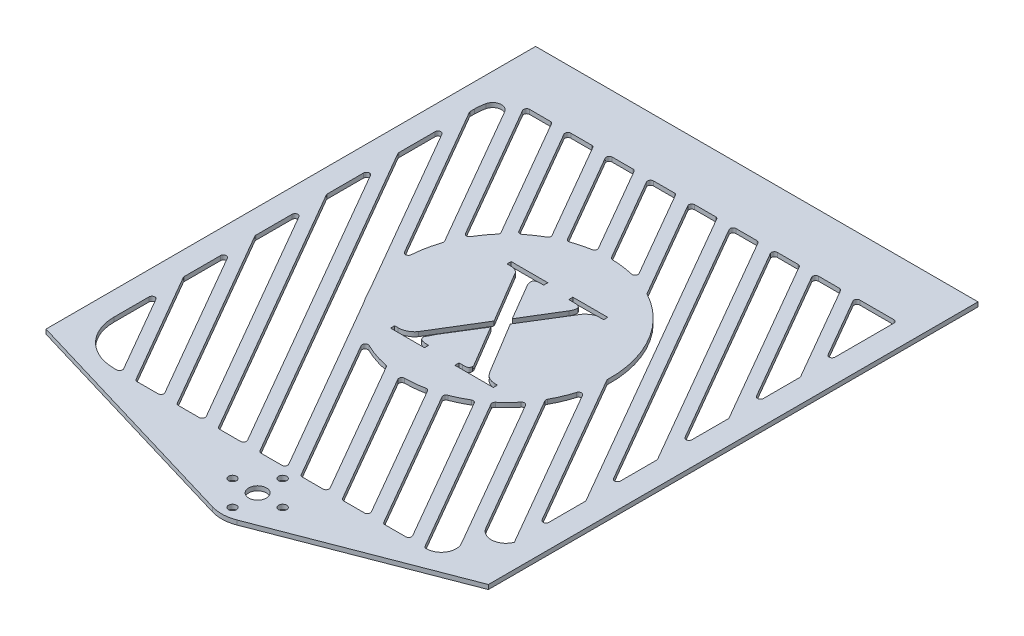
SolidWorks part; units mm, degrees
ref_plane "前视基准面" through (0, 0, 0) normal (0, 0, 1) x (1, 0, 0)
ref_plane "上视基准面" through (0, 0, 0) normal (0, 1, 0) x (1, 0, 0)
ref_plane "右视基准面" through (0, 0, 0) normal (1, 0, 0) x (0, 0, -1)
sketch "草图1" plane through (0, 0, 0) normal (0, 1, 0) x (1, 0, 0)
  circle A0 centre (0, 0) radius 12.25
  circle A1 centre (0, 0) radius 8.5 construction
  circle A2 centre (0, 8.5) radius 1.35
  circle A3 centre (8.5, 0) radius 1.35
  circle A4 centre (0, -8.5) radius 1.35
  circle A5 centre (-8.5, 0) radius 1.35
  circle A6 centre (0, 0) radius 3
  point P15 (0, 0)
  dimension "D1" = 24.5
  dimension "D2" = 17
  dimension "D3" = 2.7
  dimension "D5" = 6
  dimension "D4" = 4
extrude "凸台-拉伸1" add sketch "草图1" along normal blind 1.5
sketch "草图2" plane through (0, 1.5, 0) normal (0, 1, 0) x (1, 0, 0)
  line L0 (-84, 12.25) -> (-3.4985, -11.7398)
  line L1 (-84, 167.25) -> (66, 167.25)
  line L2 (-84, 167.25) -> (-84, 12.25)
  line L4 (66, 167.25) -> (66, 12.25)
  line L5 (4.3959, -11.4341) -> (66, 12.25)
  circle A0 centre (0, 0) radius 12.25 construction
  arc A2 (4.3959, -11.4341) -> (-3.4985, -11.7398) centre (0, 0) ccw
  dimension "D7" = 24.5
  dimension "D1" = 155
  dimension "D2" = 150
  dimension "D3" = 66
  dimension "D5" = 155
  dimension "D6" = 106.594
extrude "凸台-拉伸2" add sketch "草图2" against normal up to surface (1.5 mm away) up to face at (0, 0, 12.25)
sketch "草图4" plane through (0, 1.5, 0) normal (0, 1, 0) x (1, 0, 0)
  line L5 (-84, 167.25) -> (-84, 12.25) construction
  circle A0 centre (0, 0) radius 12.25 construction
  text T0 "X" font "新宋体" height 40
  dimension "D1" = 24.5
  dimension "D2" = 70
  dimension "D3" = 56
extrude "切除-拉伸2" cut sketch "草图4" against normal through all
sketch "草图5" plane through (0, 1.5, 0) normal (0, 1, 0) x (1, 0, 0)
  line L0 (66, 12.25) -> (66, 167.25) construction
  line L1 (66, 167.25) -> (-84, 167.25) construction
  line L2 (66, 12.25) -> (-84, 12.25)
  line L3 (66, 12.25) -> (66, 166.75)
  line L4 (66, 166.75) -> (-84, 166.75)
  line L5 (-84, 12.25) -> (-84, 166.75)
  line L7 (58, 12.25) -> (58, 158.75)
  line L8 (58, 158.75) -> (-76, 158.75)
  line L9 (-76, 12.25) -> (-76, 158.75)
  line L10 (58, 20.25) -> (-76, 20.25) construction
  line L11 (58, 20.25) -> (58, 158.75) construction
  line L12 (-76, 20.25) -> (-76, 158.75) construction
  line L13 (-53.6906, 12.25) -> (-76, 50.891)
  line L14 (-56, 12.25) -> (-76, 46.891)
  line L15 (-42, 12.25) -> (-76, 71.1397)
  line L16 (-28, 12.25) -> (-76, 95.3884)
  line L17 (-14, 12.25) -> (-76, 119.6372)
  line L18 (0, 12.25) -> (-31.5075, 66.8226)
  line L19 (14, 12.25) -> (-12.901, 58.8439)
  line L20 (28, 12.25) -> (0.471, 59.9316)
  line L21 (42, 12.25) -> (11.4265, 65.2048)
  line L22 (56, 12.25) -> (20.1779, 74.2958)
  line L23 (58, 33.0346) -> (25.6921, 88.9935)
  line L24 (58, 57.2833) -> (-0.5818, 158.75)
  line L25 (58, 81.532) -> (13.4182, 158.75)
  line L26 (58, 105.7807) -> (27.4182, 158.75)
  line L27 (-43.9794, 92.4245) -> (-76, 147.8859)
  line L29 (-39.6906, 12.25) -> (-76, 75.1397)
  line L30 (-25.6906, 12.25) -> (-76, 99.3884)
  line L31 (-11.6906, 12.25) -> (-76, 123.6372)
  line L32 (2.3094, 12.25) -> (-27.5301, 63.9335)
  line L33 (16.3094, 12.25) -> (-10.4839, 58.6573)
  line L34 (30.3094, 12.25) -> (2.427, 60.5438)
  line L35 (44.3094, 12.25) -> (13.0295, 66.4284)
  line L36 (58, 12.7859) -> (21.3707, 76.2298)
  line L37 (58, 37.0346) -> (25.9816, 92.4921)
  line L38 (58, 61.2833) -> (1.7276, 158.75)
  line L39 (58, 85.532) -> (15.7276, 158.75)
  line L40 (58, 109.7807) -> (29.7276, 158.75)
  line L41 (-43.466, 87.5353) -> (-76, 143.8859)
  line L42 (-58.3094, 12.25) -> (-76, 42.891)
  line L43 (-44.3094, 12.25) -> (-76, 67.1397)
  line L44 (-30.3094, 12.25) -> (-76, 91.3884)
  line L45 (-16.3094, 12.25) -> (-76, 115.6372)
  line L46 (-2.3094, 12.25) -> (-37.8559, 73.8183)
  line L47 (11.6906, 12.25) -> (-15.4282, 59.2212)
  line L48 (25.6906, 12.25) -> (-1.5479, 59.4284)
  line L49 (39.6906, 12.25) -> (9.7655, 64.0817)
  line L50 (53.6906, 12.25) -> (18.9052, 72.5)
  line L51 (58, 29.0346) -> (25.1457, 85.94)
  line L52 (58, 53.2833) -> (-2.8912, 158.75)
  line L53 (58, 77.532) -> (11.1088, 158.75)
  line L54 (58, 101.7807) -> (25.1088, 158.75)
  line L55 (-40.5818, 78.5397) -> (-76, 139.8859)
  line L56 (-42.0094, 105.2611) -> (-72.8912, 158.75)
  line L57 (-41.0725, 107.6384) -> (-70.5818, 158.75)
  line L58 (-40.0256, 109.825) -> (-68.2724, 158.75)
  line L59 (-34.8898, 117.1783) -> (-58.8912, 158.75)
  line L60 (-33.4445, 118.6751) -> (-56.5818, 158.75)
  line L61 (113.7321, 13.25) -> (24.5314, 167.75) construction
  line L62 (112, 12.25) -> (22.7994, 166.75) construction
  line L63 (110.2679, 11.25) -> (21.0673, 165.75) construction
  line L64 (-31.9364, 120.0629) -> (-54.2724, 158.75)
  line L65 (99.7321, 13.25) -> (10.5314, 167.75) construction
  line L66 (98, 12.25) -> (8.7994, 166.75) construction
  line L67 (96.2679, 11.25) -> (7.0673, 165.75) construction
  line L68 (-25.2032, 124.6493) -> (-44.8912, 158.75)
  line L69 (85.7321, 13.25) -> (-3.4686, 167.75) construction
  line L70 (84, 12.25) -> (-5.2006, 166.75) construction
  line L71 (82.2679, 11.25) -> (-6.9327, 165.75) construction
  line L72 (-23.4001, 125.5263) -> (-42.5818, 158.75)
  line L73 (71.7321, 13.25) -> (-17.4686, 167.75) construction
  line L74 (70, 12.25) -> (-19.2006, 166.75) construction
  line L75 (-57.7321, 11.25) -> (-146.9327, 165.75) construction
  line L76 (-56, 12.25) -> (-145.2006, 166.75) construction
  line L77 (-54.2679, 13.25) -> (-143.4686, 167.75) construction
  line L78 (-43.7321, 11.25) -> (-132.9327, 165.75) construction
  line L79 (-42, 12.25) -> (-131.2006, 166.75) construction
  line L80 (-40.2679, 13.25) -> (-129.4686, 167.75) construction
  line L81 (-29.7321, 11.25) -> (-118.9327, 165.75) construction
  line L82 (-28, 12.25) -> (-117.2006, 166.75) construction
  line L83 (-26.2679, 13.25) -> (-115.4686, 167.75) construction
  line L84 (-15.7321, 11.25) -> (-104.9327, 165.75) construction
  line L85 (-14, 12.25) -> (-103.2006, 166.75) construction
  line L86 (-12.2679, 13.25) -> (-101.4686, 167.75) construction
  line L87 (-1.7321, 11.25) -> (-90.9327, 165.75) construction
  line L88 (0, 12.25) -> (-89.2006, 166.75) construction
  line L89 (1.7321, 13.25) -> (-87.4686, 167.75) construction
  line L90 (12.2679, 11.25) -> (-76.9327, 165.75) construction
  line L91 (14, 12.25) -> (-75.2006, 166.75) construction
  line L92 (-21.5389, 126.3027) -> (-40.2724, 158.75)
  line L93 (15.7321, 13.25) -> (-73.4686, 167.75) construction
  line L94 (26.2679, 11.25) -> (-62.9327, 165.75) construction
  line L95 (28, 12.25) -> (-61.2006, 166.75) construction
  line L96 (-13.3429, 128.3554) -> (-30.8912, 158.75)
  line L97 (29.7321, 13.25) -> (-59.4686, 167.75) construction
  line L98 (40.2679, 11.25) -> (-48.9327, 165.75) construction
  line L99 (42, 12.25) -> (-47.2006, 166.75) construction
  line L100 (-11.1514, 128.5596) -> (-28.5818, 158.75)
  line L101 (43.7321, 13.25) -> (-45.4686, 167.75) construction
  line L102 (54.2679, 11.25) -> (-34.9327, 165.75) construction
  line L103 (56, 12.25) -> (-33.2006, 166.75) construction
  line L104 (-8.8801, 128.6256) -> (-26.2724, 158.75)
  line L105 (57.7321, 13.25) -> (-31.4686, 167.75) construction
  line L106 (68.2679, 11.25) -> (-20.9327, 165.75) construction
  line L107 (58, 134.0295) -> (43.7276, 158.75)
  line L108 (58, 130.0295) -> (41.4182, 158.75)
  line L109 (58, 126.0295) -> (39.1088, 158.75)
  line L110 (1.4167, 127.0398) -> (-16.8912, 158.75)
  line L111 (4.3344, 125.9862) -> (-14.5818, 158.75)
  line L112 (7.5089, 124.4877) -> (-12.2724, 158.75)
  circle A0 centre (-9, 93.6258) radius 35
  point P2 (48.5544, 142.3897)
  dimension "D1" = 75
  dimension "D2" = 70
  dimension "D3" = 2
  dimension "D4" = 2
  dimension "D6" = 14.2724
  dimension "D7" = 24.7205
  dimension "D8" = 4
  dimension "D9" = 2
  dimension "D5" = 8
extrude "切除-拉伸3" cut sketch "草图5" against normal blind 10 contours L2 L42 L9 | L2 L43 L9 L13 | L2 L44 L9 L29 | L2 L45 L9 L30 | A0 L55 L9 L31 L2 L46 | A0 L32 L2 L47 | A0 L33 L2 L48 | A0 L56 L8 L9 L27 | A0 L59 L8 L58 | A0 L68 L8 L64 | A0 L96 L8 L92 | A0 L110 L8 L104 | A0 L37 L7 L52 L8 L112 | A0 L36 L7 L51 | A0 L35 L2 L50 | A0 L34 L2 L49 | L7 L53 L8 L38 | L7 L54 L8 L39 | L7 L109 L8 L40 | L107 L7 L8 region at (40.695, 1.5, -50.7346) region at (32.5956, 1.5, -40.8071) region at (-70.1031, 1.5, -22.4637) region at (26.0815, 1.5, -100.7704) region at (20.6373, 1.5, -37.223) region at (-62.3642, 1.5, -35.8679) region at (32.138, 1.5, -113.9557) region at (7.558, 1.5, -35.555) region at (-12.6987, 1.5, -143.4323) region at (-55.4106, 1.5, -47.912) region at (39.1115, 1.5, -126.0342) region at (-7.161, 1.5, -36.6511) region at (-26.6039, 1.5, -143.1107) region at (-48.4333, 1.5, -59.9969) region at (46.0536, 1.5, -138.0582) region at (-41.4476, 1.5, -72.0964) region at (-39.2005, 1.5, -140.5978) region at (53.2425, 1.5, -150.5098) region at (-59.4085, 1.5, -127.2582) region at (-50.6714, 1.5, -136.168)
fillet "圆角3" radius 15 2 edges at (-76, 0.75, -158.75) (-76, 0.75, -12.25)
fillet "圆角4" radius 3 1 edges at (-72.8912, 0.75, -158.75)
fillet "圆角5" radius 5 2 edges at (53.6906, 0.75, -12.25) (58, 0.75, -12.7859)
sketch "草图6" plane through (0, 1.5, 0) normal (0, 1, 0) x (1, 0, 0)
  line L1 (66, 167.25) -> (-84, 167.25)
  line L2 (66, 167.25) -> (66, 178.25)
  line L3 (66, 178.25) -> (-84, 178.25)
  line L4 (-84, 167.25) -> (-84, 178.25)
  dimension "D1" = 150
  dimension "D2" = 11
extrude "凸台-拉伸3" add sketch "草图6" against normal up to surface (1.5 mm away) up to face at (23.1488, 0, -104.5723)
fillet "圆角6" radius 1 77 edges at (58, 0.75, -134.0295) (58, 0.75, -158.75) (43.7276, 0.75, -158.75) (58, 0.75, -126.0295) (39.1088, 0.75, -158.75) (29.7276, 0.75, -158.75) (58, 0.75, -109.7807) (58, 0.75, -101.7807) (25.1088, 0.75, -158.75) (15.7276, 0.75, -158.75) (58, 0.75, -85.532) (58, 0.75, -77.532) (11.1088, 0.75, -158.75) (1.7276, 0.75, -158.75) (58, 0.75, -61.2833) (2.427, 0.75, -60.5438) (30.3094, 0.75, -12.25) (39.6906, 0.75, -12.25) (9.7655, 0.75, -64.0817) (13.0295, 0.75, -66.4284) (44.3094, 0.75, -12.25) (18.9052, 0.75, -72.5) (21.3707, 0.75, -76.2298) (25.1457, 0.75, -85.94) (25.9816, 0.75, -92.4921) (58, 0.75, -37.0346) (58, 0.75, -53.2833) (-2.8912, 0.75, -158.75) (-12.2724, 0.75, -158.75) (7.5089, 0.75, -124.4877) (1.4167, 0.75, -127.0398) (-16.8912, 0.75, -158.75) (-26.2724, 0.75, -158.75) (-8.8801, 0.75, -128.6256) (-13.3429, 0.75, -128.3554) (-30.8912, 0.75, -158.75) (-40.2724, 0.75, -158.75) (-21.5389, 0.75, -126.3027) (-25.2032, 0.75, -124.6493) (-44.8912, 0.75, -158.75) (-54.2724, 0.75, -158.75) (-31.9364, 0.75, -120.0629) (-34.8898, 0.75, -117.1783) (-58.8912, 0.75, -158.75) (-40.0256, 0.75, -109.825) (-42.0094, 0.75, -105.2611) (-76, 0.75, -147.8859) (-43.9794, 0.75, -92.4245) (-10.4839, 0.75, -58.6573) (16.3094, 0.75, -12.25) (25.6906, 0.75, -12.25) (-1.5479, 0.75, -59.4284) (-27.5301, 0.75, -63.9335) (2.3094, 0.75, -12.25) (11.6906, 0.75, -12.25) (-15.4282, 0.75, -59.2212) (-40.5818, 0.75, -78.5397) (-76, 0.75, -139.8859) (-76, 0.75, -123.6372) (-11.6906, 0.75, -12.25) (-2.3094, 0.75, -12.25) (-37.8559, 0.75, -73.8183) (-16.3094, 0.75, -12.25) (-76, 0.75, -115.6372) (-76, 0.75, -99.3884) (-25.6906, 0.75, -12.25) (-30.3094, 0.75, -12.25) (-76, 0.75, -91.3884) (-76, 0.75, -75.1397) (-39.6906, 0.75, -12.25) (-44.3094, 0.75, -12.25) (-76, 0.75, -67.1397) (-76, 0.75, -50.891) (-53.6906, 0.75, -12.25) (-58.3094, 0.75, -12.25) (-76, 0.75, -42.891) (-68.2724, 0.75, -158.75)
